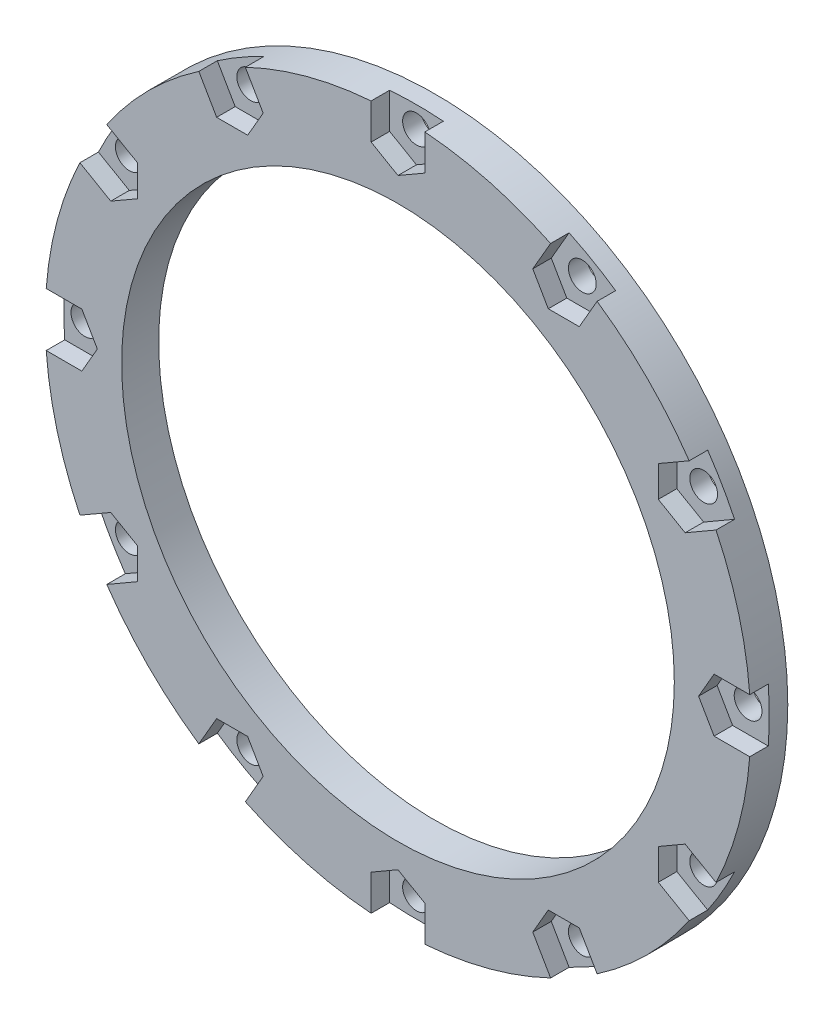
SolidWorks part; units mm, degrees
ref_plane "Front Plane" through (0, 0, 0) normal (0, 0, 1) x (1, 0, 0)
ref_plane "Top Plane" through (0, 0, 0) normal (0, 1, 0) x (1, 0, 0)
ref_plane "Right Plane" through (0, 0, 0) normal (1, 0, 0) x (0, 0, -1)
sketch "Sketch1" plane through (0, 0, 0) normal (0, 0, 1) x (1, 0, 0)
  circle A0 centre (0, 0) radius 38.1
  circle A1 centre (0, 0) radius 29.845
  dimension "D1" = 76.2
  dimension "D2" = 59.69
extrude "Boss-Extrude1" add sketch "Sketch1" along normal blind 4
sketch "Sketch2" plane through (0, 0, 4) normal (0, 0, 1) x (1, 0, 0)
  line L0 (0, 0) -> (0, 44.3901) construction
  circle A0 centre (0, 0) radius 35.814 construction
  circle A1 centre (0, 35.814) radius 1.5
  circle A2 centre (17.907, 31.0158) radius 1.5
  circle A3 centre (31.0158, 17.907) radius 1.5
  circle A4 centre (35.814, 0) radius 1.5
  circle A5 centre (31.0158, -17.907) radius 1.5
  circle A6 centre (17.907, -31.0158) radius 1.5
  circle A7 centre (0, -35.814) radius 1.5
  circle A8 centre (-17.907, -31.0158) radius 1.5
  circle A9 centre (-31.0158, -17.907) radius 1.5
  circle A10 centre (-35.814, 0) radius 1.5
  circle A11 centre (-31.0158, 17.907) radius 1.5
  circle A12 centre (-17.907, 31.0158) radius 1.5
  point P30 (0, 0)
  dimension "D1" = 71.628
  dimension "D2" = 3
  dimension "D3" = 12
extrude "Cut-Extrude1" cut sketch "Sketch2" against normal through all
sketch "Sketch3" plane through (0, 0, 4) normal (0, 0, 1) x (1, 0, 0)
  line L0 (0, 0) -> (0, 45.6158) construction
  line L1 (-2.9, 37.9895) -> (0, 39.1626)
  line L2 (16.4833, 34.3498) -> (19.5813, 33.9158)
  line L3 (-2.9, 37.9895) -> (-2.9, 34.1397)
  line L4 (-2.9, 34.1397) -> (0, 32.4654)
  line L5 (0, 32.4654) -> (2.9, 34.1397)
  line L6 (2.9, 34.1397) -> (2.9, 37.9895)
  line L7 (16.4833, 34.3498) -> (14.5584, 31.0158)
  line L8 (2.9, 37.9895) -> (0, 39.1626)
  line L9 (14.5584, 31.0158) -> (16.2327, 28.1158)
  line L10 (16.2327, 28.1158) -> (19.5813, 28.1158)
  line L11 (19.5813, 28.1158) -> (21.5062, 31.4498)
  line L12 (21.5062, 31.4498) -> (19.5813, 33.9158)
  line L13 (31.4498, 21.5062) -> (33.9158, 19.5813)
  line L14 (31.4498, 21.5062) -> (28.1158, 19.5813)
  line L15 (28.1158, 19.5813) -> (28.1158, 16.2327)
  line L16 (28.1158, 16.2327) -> (31.0158, 14.5584)
  line L17 (31.0158, 14.5584) -> (34.3498, 16.4833)
  line L18 (34.3498, 16.4833) -> (33.9158, 19.5813)
  line L19 (37.9895, 2.9) -> (39.1626, 0)
  line L20 (37.9895, 2.9) -> (34.1397, 2.9)
  line L21 (34.1397, 2.9) -> (32.4654, 0)
  line L22 (32.4654, 0) -> (34.1397, -2.9)
  line L23 (34.1397, -2.9) -> (37.9895, -2.9)
  line L24 (37.9895, -2.9) -> (39.1626, 0)
  line L25 (34.3498, -16.4833) -> (33.9158, -19.5813)
  line L26 (34.3498, -16.4833) -> (31.0158, -14.5584)
  line L27 (31.0158, -14.5584) -> (28.1158, -16.2327)
  line L28 (28.1158, -16.2327) -> (28.1158, -19.5813)
  line L29 (28.1158, -19.5813) -> (31.4498, -21.5062)
  line L30 (31.4498, -21.5062) -> (33.9158, -19.5813)
  line L31 (21.5062, -31.4498) -> (19.5813, -33.9158)
  line L32 (21.5062, -31.4498) -> (19.5813, -28.1158)
  line L33 (19.5813, -28.1158) -> (16.2327, -28.1158)
  line L34 (16.2327, -28.1158) -> (14.5584, -31.0158)
  line L35 (14.5584, -31.0158) -> (16.4833, -34.3498)
  line L36 (16.4833, -34.3498) -> (19.5813, -33.9158)
  line L37 (2.9, -37.9895) -> (0, -39.1626)
  line L38 (2.9, -37.9895) -> (2.9, -34.1397)
  line L39 (2.9, -34.1397) -> (0, -32.4654)
  line L40 (0, -32.4654) -> (-2.9, -34.1397)
  line L41 (-2.9, -34.1397) -> (-2.9, -37.9895)
  line L42 (-2.9, -37.9895) -> (0, -39.1626)
  line L43 (-16.4833, -34.3498) -> (-19.5813, -33.9158)
  line L44 (-16.4833, -34.3498) -> (-14.5584, -31.0158)
  line L45 (-14.5584, -31.0158) -> (-16.2327, -28.1158)
  line L46 (-16.2327, -28.1158) -> (-19.5813, -28.1158)
  line L47 (-19.5813, -28.1158) -> (-21.5062, -31.4498)
  line L48 (-21.5062, -31.4498) -> (-19.5813, -33.9158)
  line L49 (-31.4498, -21.5062) -> (-33.9158, -19.5813)
  line L50 (-31.4498, -21.5062) -> (-28.1158, -19.5813)
  line L51 (-28.1158, -19.5813) -> (-28.1158, -16.2327)
  line L52 (-28.1158, -16.2327) -> (-31.0158, -14.5584)
  line L53 (-31.0158, -14.5584) -> (-34.3498, -16.4833)
  line L54 (-34.3498, -16.4833) -> (-33.9158, -19.5813)
  line L55 (-37.9895, -2.9) -> (-39.1626, 0)
  line L56 (-37.9895, -2.9) -> (-34.1397, -2.9)
  line L57 (-34.1397, -2.9) -> (-32.4654, 0)
  line L58 (-32.4654, 0) -> (-34.1397, 2.9)
  line L59 (-34.1397, 2.9) -> (-37.9895, 2.9)
  line L60 (-37.9895, 2.9) -> (-39.1626, 0)
  line L61 (-34.3498, 16.4833) -> (-33.9158, 19.5813)
  line L62 (-34.3498, 16.4833) -> (-31.0158, 14.5584)
  line L63 (-31.0158, 14.5584) -> (-28.1158, 16.2327)
  line L64 (-28.1158, 16.2327) -> (-28.1158, 19.5813)
  line L65 (-28.1158, 19.5813) -> (-31.4498, 21.5062)
  line L66 (-31.4498, 21.5062) -> (-33.9158, 19.5813)
  line L67 (-21.5062, 31.4498) -> (-19.5813, 33.9158)
  line L68 (-21.5062, 31.4498) -> (-19.5813, 28.1158)
  line L69 (-19.5813, 28.1158) -> (-16.2327, 28.1158)
  line L70 (-16.2327, 28.1158) -> (-14.5584, 31.0158)
  line L71 (-14.5584, 31.0158) -> (-16.4833, 34.3498)
  line L72 (-16.4833, 34.3498) -> (-19.5813, 33.9158)
  line L139 (0, 39.1626) -> (-1.45, 38.3255) [skipped]
  line L140 (2.9, 37.4883) -> (1.9248, 38.0513) [skipped]
  circle A0 centre (0, 35.814) radius 2.9 construction
  circle A1 centre (0, 0) radius 38.1 construction
  circle A2 centre (17.907, 31.0158) radius 2.9 construction
  circle A3 centre (31.0158, 17.907) radius 2.9 construction
  circle A4 centre (35.814, 0) radius 2.9 construction
  circle A5 centre (31.0158, -17.907) radius 2.9 construction
  circle A6 centre (17.907, -31.0158) radius 2.9 construction
  circle A7 centre (0, -35.814) radius 2.9 construction
  circle A8 centre (-17.907, -31.0158) radius 2.9 construction
  circle A9 centre (-31.0158, -17.907) radius 2.9 construction
  circle A10 centre (-35.814, 0) radius 2.9 construction
  circle A11 centre (-31.0158, 17.907) radius 2.9 construction
  circle A12 centre (-17.907, 31.0158) radius 2.9 construction
  point P103 (0, 0)
  point P105 (0, 0)
  dimension "D1" = 5.8
  dimension "D2" = 12
extrude "Cut-Extrude2" cut sketch "Sketch3" against normal blind 2
